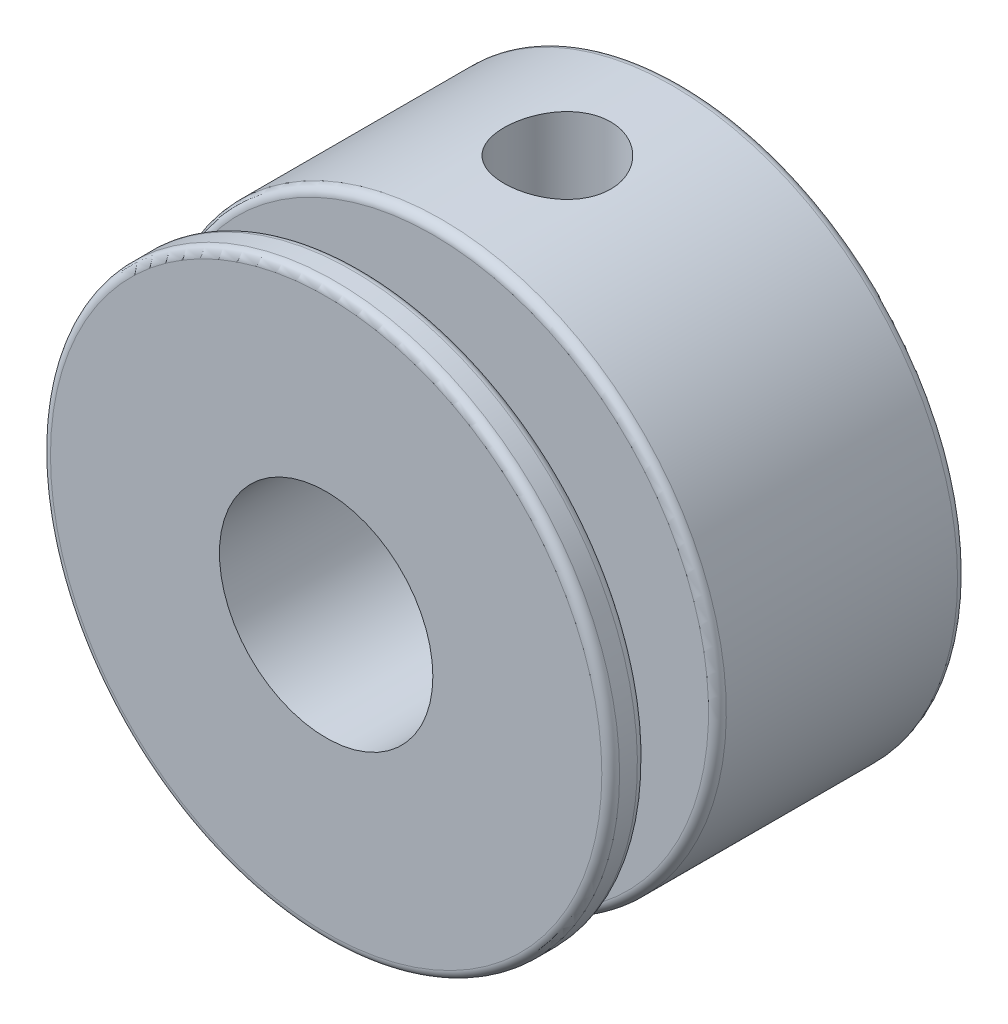
SolidWorks part; units mm, degrees
ref_plane "Front Plane" through (0, 0, 0) normal (0, 0, 1) x (1, 0, 0)
ref_plane "Top Plane" through (0, 0, 0) normal (0, 1, 0) x (1, 0, 0)
ref_plane "Right Plane" through (0, 0, 0) normal (1, 0, 0) x (0, 0, -1)
sketch "Sketch1" plane through (0, 0, 0) normal (0, 0, 1) x (1, 0, 0)
  circle A0 centre (0, 0) radius 8
  dimension "D1" = 16
extrude "Boss-Extrude1" add sketch "Sketch1" along normal blind 10 contours A0
sketch "Sketch2" plane through (0, 0, 0) normal (1, 0, 0) x (0, 0, -1)
  line L0 (0, 8) -> (-10, 8) construction
  line L1 (-9, 8) -> (-7, 8)
  line L2 (-9, 8) -> (-9, 5)
  line L3 (-9, 5) -> (-7, 5)
  line L4 (-7, 8) -> (-7, 5)
  line L5 (-10, 8) -> (-10, -8) construction
  dimension "D1" = 3
  dimension "D2" = 0
  dimension "D3" = 2
  dimension "D4" = 1
sketch "Sketch3" plane through (0, 0, 0) normal (1, 0, 0) x (0, 0, -1)
  line L0 (5.2495, 0) -> (-14.7505, 0)
  dimension "D1" = 20
revolve "Cut-Revolve2" cut sketch "Sketch2" angle 360 about L0
sketch "Sketch5" plane through (0, 0, 0) normal (0, 1, 0) x (1, 0, 0)
  line L1 (0, 5.2495) -> (0, -14.7505) construction
  line L2 (8, 0) -> (-8, 0) construction
  circle A1 centre (0, -3.5) radius 1.5
  dimension "D1" = 3
  dimension "D2" = 3.5
extrude "Cut-Extrude1" cut sketch "Sketch5" along normal up to next from offset 2.5 contours A1
sketch "Sketch6" plane through (0, 0, 0) normal (0, 0, 1) x (1, 0, 0)
  circle A0 centre (0, 0) radius 3
  dimension "D1" = 6
extrude "Cut-Extrude2" cut sketch "Sketch6" along normal up to next
fillet "Fillet3" radius 0.25 1 edges at (0, 8, 9)
fillet "Fillet4" radius 0.25 1 edges at (0, 8, 7)
fillet "Fillet5" radius 0.25 2 edges at (8, 0, 0) (8, 0, 10)
